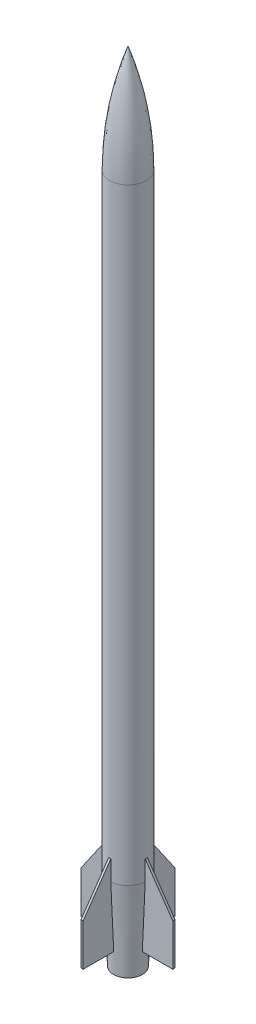
SolidWorks part; units mm, degrees
ref_plane "Front Plane"
ref_plane "Top Plane" through (0, 0, 0) normal (0, 1, 0) x (1, 0, 0)
ref_plane "Right Plane" through (0, 0, 0) normal (1, 0, 0) x (0, 0, -1)
sketch "Sketch2" plane through (0, 0, 0) normal (0, 0, 1) x (1, 0, 0)
  line L0 (0, 0) -> (0, 3700)
  line L1 (85, 3201.2283) -> (85, 384.2507)
  line L2 (85, 384.2507) -> (67.1774, 0)
  line L3 (67.1774, 0) -> (0, 0)
  spline S0 degree 2 poles (0, 3700) (84.8652, 3457.5166) (85, 3201.2283) knots 0 0 0 1 1 1
  dimension "D1" = 3700
  dimension "D2" = 85
revolve "Revolve1" add sketch "Sketch2" angle 360 about L0
ref_axis "Axis1" [suppressed] through (0, 3700, 0) along (0, -1, 0)
sketch "Sketch3" plane through (0, 0, 0) normal (1, 0, 0) x (0, 0, -1)
  line L0 (45.9001, 532.6799) -> (45.9001, 96.5669)
  line L1 (45.9001, 96.5669) -> (213.375, 96.5669)
  line L2 (213.375, 96.5669) -> (213.375, 291.1105)
  line L3 (213.375, 291.1105) -> (45.9001, 532.6799)
  dimension "D1" = 167.4749
  dimension "D2" = 436.113
  dimension "D3" = 194.5436
extrude "Boss-Extrude1" add sketch "Sketch3" along normal mid plane 10
pattern_circular "CirPattern1" count 4 over 360 about axis through (0, 3700, 0) along (0, -1, 0) of "Boss-Extrude1"
